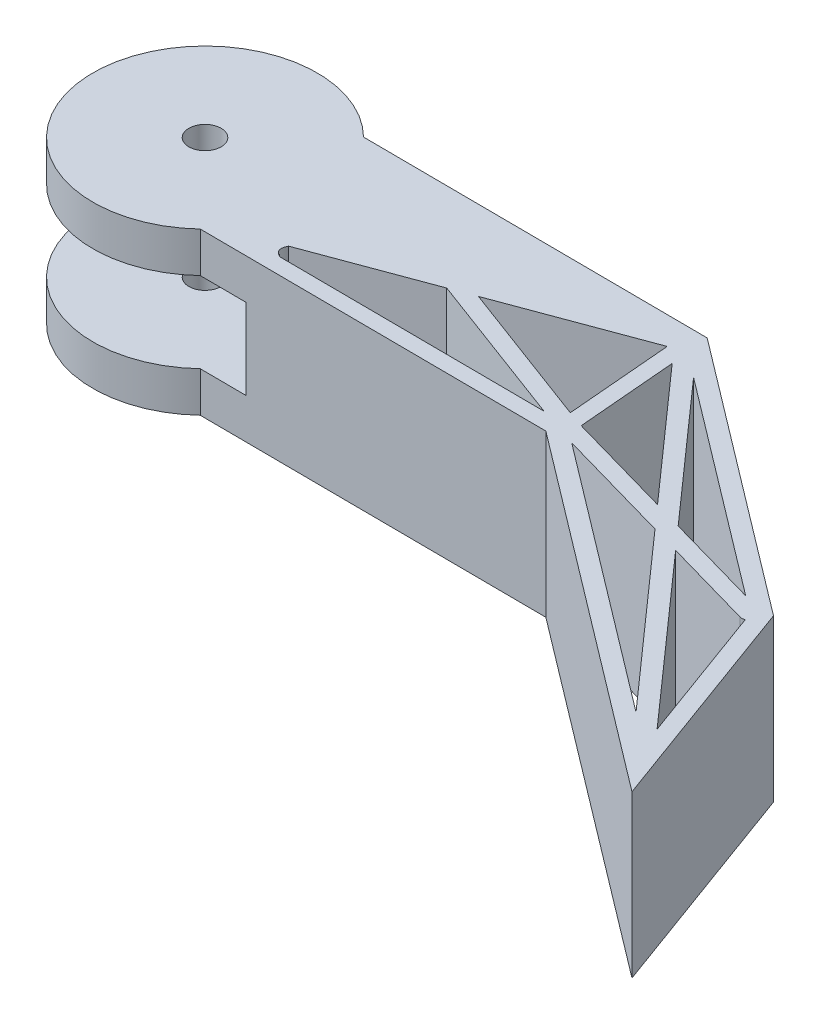
SolidWorks part; units mm, degrees
ref_plane "Front Plane" through (0, 0, 0) normal (0, 0, 1) x (1, 0, 0)
ref_plane "Top Plane" through (0, 0, 0) normal (0, 1, 0) x (1, 0, 0)
ref_plane "Right Plane" through (0, 0, 0) normal (1, 0, 0) x (0, 0, -1)
sketch "Sketch2" plane through (0, 0, 0) normal (0, 1, 0) x (1, 0, 0)
  line L0 (-86.903, -5.6011) -> (-1.9458, -5.6011) construction
  line L1 (-2.39, -19.0095) -> (53.5769, -61.4158)
  line L2 (53.5769, -61.4158) -> (40.7254, -26.2781)
  line L3 (-56.8329, 6.7281) -> (-2.3899, 6.3905)
  line L4 (40.7254, -26.2781) -> (-2.3899, 6.3905)
  line L6 (-57.1469, -18.67) -> (-2.39, -19.0095)
  arc A0 (-57.1469, -18.67) -> (-56.8329, 6.7281) centre (-69.2509, -5.8194) cw
  circle A1 centre (-69.2509, -5.8194) radius 2.54
  dimension "D3" = 25.4
extrude "Boss-Extrude4" add sketch "Sketch2" along normal blind 12.7
sketch "Sketch4" plane through (0, 12.7, 0) normal (0, 1, 0) x (1, 0, 0)
  circle A0 centre (-69.2509, -5.8194) radius 17.6534
extrude "Cut-Extrude1" cut sketch "Sketch4" against normal blind 6.35
sketch "Triangleout" plane through (0, 6.35, 0) normal (0, 1, 0) x (1, 0, 0)
  line L0 (-58.1063, -19.5103) -> (-49.4554, -19.5103)
  line L1 (-49.4554, -19.5103) -> (-53.0939, -12.9324)
  line L2 (-53.0939, -12.9324) -> (-58.1063, -19.5103)
  arc A0 (-57.1469, -18.67) -> (-56.8329, 6.7281) centre (-69.2509, -5.8194) ccw construction
  arc A1 (-56.8329, 6.7281) -> (-57.1469, -18.67) centre (-69.2509, -5.8194) ccw construction
extrude "Cut-Extrude2" cut sketch "Triangleout" along normal blind 6.35
mirror "Mirror3" about plane through (-69.2509, 12.7, 5.8194) normal (0, -1, 0) of "Cut-Extrude2", "Cut-Extrude1", "Boss-Extrude4"
sketch "Sketch5" plane through (0, 25.4, 0) normal (0, 1, 0) x (1, 0, 0)
  line L0 (-1.5294, -16.4748) -> (-3.2505, 3.8558) construction
  line L1 (48.2231, -54.1724) -> (-3.2505, 3.8558)
  line L2 (47.1512, -43.847) -> (-2.39, -6.3095) construction
  line L3 (-57.1312, -16.1301) -> (-3.2505, 3.8558)
  line L4 (53.5769, -61.4158) -> (40.7254, -26.2781) construction
  line L5 (-56.9899, -5.971) -> (-2.39, -6.3095) construction
  line L6 (-57.1469, -18.67) -> (-56.8329, 6.7281) construction
  line L7 (-56.8486, 4.1881) -> (-1.5294, -16.4748)
  line L8 (-1.5294, -16.4748) -> (38.5964, -27.8518)
  line L10 (-56.6895, -17.3208) -> (-3.6238, 2.3628)
  line L11 (47.273, -55.0152) -> (-3.6238, 2.3628)
  line L12 (-57.293, 2.9984) -> (-1.9254, -17.6825)
  line L13 (-1.9254, -17.6825) -> (38.25, -29.0736)
  line L14 (-57.5729, -14.9393) -> (-2.8772, 5.3488)
  line L15 (49.1732, -53.3296) -> (-2.8772, 5.3488)
  line L16 (-56.4043, 5.3778) -> (-1.1333, -15.267)
  line L17 (-1.1333, -15.267) -> (38.9428, -26.6299)
  line L18 (-1.5294, -16.4748) -> (-3.2505, 3.8558)
  line L19 (-0.2639, -16.3676) -> (-1.9851, 3.963)
  line L20 (-2.7949, -16.5819) -> (-4.516, 3.7487)
  line L28 (-3.2505, 3.8558) -> (-56.8486, 4.1881)
  line L29 (38.5964, -27.8518) -> (-3.2505, 3.8558)
  line L30 (48.2231, -54.1724) -> (38.5964, -27.8518)
  line L31 (-1.5294, -16.4748) -> (48.2231, -54.1724)
  line L32 (-57.1312, -16.1301) -> (-1.5294, -16.4748)
  line L33 (-3.2505, 3.8558) -> (-56.8486, 4.1881)
  line L34 (38.5964, -27.8518) -> (-3.2505, 3.8558)
  line L35 (48.2231, -54.1724) -> (38.5964, -27.8518)
  line L36 (-1.5294, -16.4748) -> (48.2231, -54.1724)
  line L37 (-57.1312, -16.1301) -> (-1.5294, -16.4748)
  arc A0 (-56.6895, -17.3208) -> (-57.5729, -14.9393) centre (-57.1312, -16.1301) cw
  arc A1 (47.273, -55.0152) -> (49.1732, -53.3296) centre (48.2231, -54.1724) ccw
  arc A2 (-57.293, 2.9984) -> (-56.4043, 5.3778) centre (-56.8486, 4.1881) cw
  arc A3 (38.25, -29.0736) -> (38.9428, -26.6299) centre (38.5964, -27.8518) ccw
  arc A4 (-0.2639, -16.3676) -> (-2.7949, -16.5819) centre (-1.5294, -16.4748) cw
  arc A5 (-1.9851, 3.963) -> (-4.516, 3.7487) centre (-3.2505, 3.8558) ccw
  arc A7 (-57.1469, -18.67) -> (-56.8329, 6.7281) centre (-69.6889, -5.814) ccw
  spline S0 degree 1 poles (-57.1312, -16.1301) (-56.8486, 4.1881) knots 0 0 1 1
  spline S1 degree 2 poles (-47.0825, -16.1924) (-48.6344, -15.5095) (-47.8598, -14.0456) knots 0 0 0 1 1 1
  dimension "D1" = 2.54
  dimension "D2" = 1.27
  dimension "D3" = 1.27
  dimension "D4" = 1.27
  dimension "D5" = 1.27
extrude "Cut-Extrude5" cut sketch "Sketch5" against normal through all contours L10 L37 L12 | L14 L33 L16 | L16 L20 L10 | A3 L13 L15 L35 | L13 L36 L11 | L17 L34 L15 | L19 L17 L11 region at (36.756, 25.4, 35.0972) region at (21.2871, 25.4, 30.8694) region at (4.8107, 25.4, 11.8628) region at (19.5694, 25.4, 15.7811) region at (-28.9114, 25.4, 13.242) region at (-11.1317, 25.4, 6.1523) region at (-29.8984, 25.4, -1.1482)
sketch "Sketch6" plane through (0, 0, 0) normal (0, -1, 0) x (1, 0, 0)
  line L0 (-29.695, 4.5986) -> (-6.8423, -3.8781)
  line L1 (-6.8423, -3.8781) -> (-53.1578, -4.1652)
  line L2 (-53.1578, -4.1652) -> (-29.695, 4.5986)
extrude "Boss-Extrude5" add sketch "Sketch6" against normal up to surface (25.4 mm away) up to face at (19.5694, 25.4, 15.7811)
